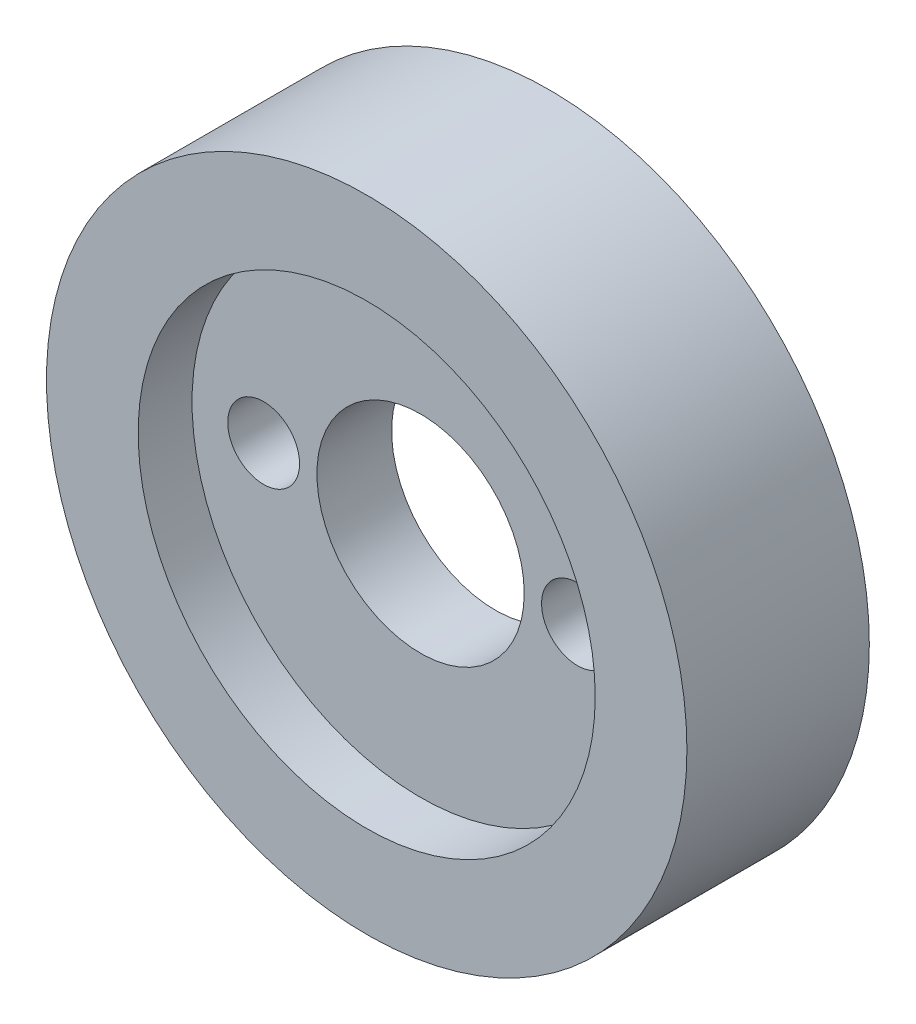
SolidWorks part; units mm, degrees
ref_plane "Front Plane" through (0, 0, 0) normal (0, 0, 1) x (1, 0, 0)
ref_plane "Top Plane" through (0, 0, 0) normal (0, 1, 0) x (1, 0, 0)
ref_plane "Right Plane" through (0, 0, 0) normal (1, 0, 0) x (0, 0, -1)
sketch "Sketch1" plane through (0, 0, 0) normal (0, 0, 1) x (1, 0, 0)
  circle A0 centre (0, 0) radius 9.8091
  circle A1 centre (0, 0) radius 3.175
  dimension "D1" = 19.6182
  dimension "D2" = 6.35
extrude "Boss-Extrude1" add sketch "Sketch1" along normal mid plane 5.588
sketch "Sketch2" plane through (0, 0, 2.794) normal (0, 0, 1) x (1, 0, 0)
  line L0 (0, 0) -> (0, 1.2313) construction
  line L1 (-7, 0) -> (-3.075, 0)
  circle A0 centre (0, 0) radius 7
  circle A1 centre (0, 0) radius 3.075
  circle A2 centre (-4.8069, 0) radius 1.1
  circle A3 centre (4.8069, 0) radius 1.1
  point P12 (0, 0)
  circle M2 centre (0, 0) radius 3.175
  dimension "D1" = 14
  dimension "D2" = 6.15
  dimension "D3" = 2.2
  dimension "D4" = 9.6139
extrude "Cut-Extrude1" cut sketch "Sketch2" against normal blind 1.65 contours A2 A0 A3 M2 region at (0, 6.802, 2.794)
mirror "Mirror1" about plane through (0, 0, 0) normal (0, 0, 1) of "Cut-Extrude1"
extrude "Cut-Extrude2" cut sketch "Sketch2<3>" against normal through all contours L1 A2 | L1 A2 | A3 region at (-4.8069, -0.4669, 2.794) region at (-4.8069, 0.4669, 2.794) region at (4.8069, 0, 2.794)
sketch "Sketch2<3>" plane through (0, 0, 2.794) normal (0, 0, 1) x (1, 0, 0) same geometry as "Sketch2"
